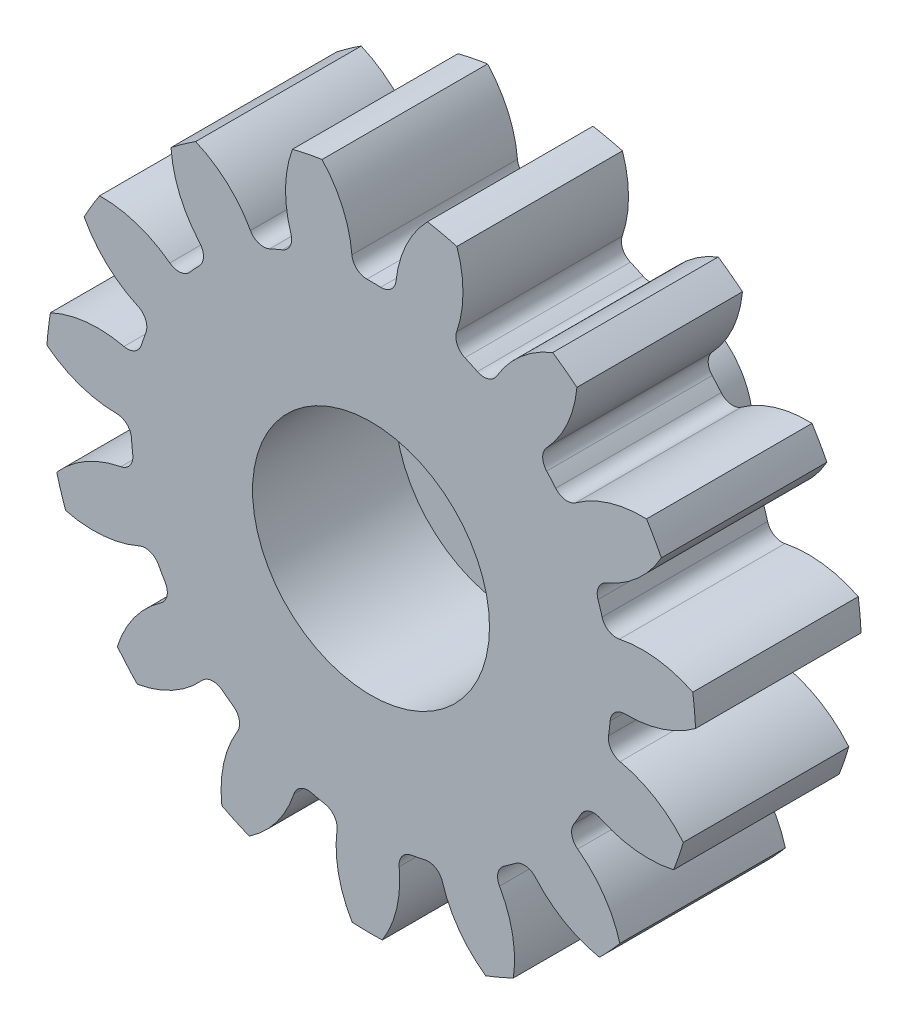
SolidWorks part; units mm, degrees
material "ABS"
ref_plane "Front" through (0, 0, 0) normal (0, 0, 1) x (1, 0, 0)
ref_plane "Top" through (0, 0, 0) normal (0, 1, 0) x (1, 0, 0)
ref_plane "Right" through (0, 0, 0) normal (1, 0, 0) x (0, 0, -1)
sketch "Sketch3" plane through (0, 0, 0) normal (0, 0, 1) x (1, 0, 0)
  circle A0 centre (0, 0) radius 21.59
  dimension "od" = 43.18
extrude "gearBody" add sketch "Sketch3" along normal blind 11
sketch "Sketch2" plane through (0, 0, 0) normal (0, 0, 1) x (1, 0, 0)
  line L0 (0, 0) -> (17.0393, 7.0579) construction
  line L1 (22.0105, -8.0941) -> (0, 0) construction
  line L2 (0, 0) -> (36.3143, 0) construction
  line L3 (19.0486, -0.229) -> (18.5878, -4.1711) construction
  line L5 (18.8182, -2.2) -> (0, 0) construction
  line L7 (0, 0) -> (18.4432, 0) construction
  arc A0 (18.4395, -0.3701) -> (18.0276, -3.8932) centre (0, 0) ccw construction
  arc A1 (21.5666, 1.0048) -> (20.7532, -5.9524) centre (0, 0) ccw construction
  arc A2 (19.0486, -0.229) -> (18.5878, -4.1711) centre (0, 0) ccw construction
  arc A3 (15.7838, -2.3046) -> (15.8898, -1.3984) centre (0, 0) ccw
  arc A4 (22.0105, -8.0941) -> (16.5506, -3.4102) centre (14.9518, -10.798) ccw
  arc A5 (22.0105, -8.0941) -> (23.2839, 2.7987) centre (0, 0) ccw
  arc A6 (23.2839, 2.7987) -> (16.8909, -0.4995) centre (17.0393, 7.0579) cw
  arc A7 (15.8898, -1.3984) -> (16.8909, -0.4995) centre (16.8715, -1.4848) cw
  arc A8 (16.5506, -3.4102) -> (15.7838, -2.3046) centre (16.759, -2.4469) cw
  point P6 (23.2839, 2.7987)
  point P22 (22.0105, -8.0941)
  dimension "baseDia" = 36.8864
  dimension "od" = 43.18
  dimension "pd" = 38.1
  dimension "rd" = 31.9024
  dimension "rFillet" = 0.9855
  dimension "pointX" = 23.2839
  dimension "pointY" = 2.7987
  dimension "CTT" = 3.9421
  dimension "flankCenterAngle" = 22.5
extrude "toothCut" cut sketch "Sketch2" along normal through all
pattern_circular "CirPattern1" count 15 over 360 about axis through (0, 0, 11) along (0, 0, -1) of "toothCut"
sketch "hub1Dia" plane through (0, 0, 0) normal (0, 0, -1) x (-1, 0, 0)
  circle A0 centre (0, 0) radius 12.7
  dimension "hub1Dia" = 25.4
sketch "hub2Dia" plane through (0, 0, 11) normal (0, 0, 1) x (1, 0, 0)
  circle A0 centre (0, 0) radius 12.7
  dimension "hub2dia" = 25.4
sketch "boreDia" plane through (0, 0, 0) normal (0, 0, 1) x (1, 0, 0)
  circle A0 centre (0, 0) radius 7.874
  dimension "boreDia" = 15.748
extrude "bore" cut sketch "boreDia" against normal mid plane 25400
sketch "Sketch4" plane through (0, 0, 0) normal (1, 0, 0) x (0, 0, -1)
  line L0 (0, 0) -> (29.4347, 0) construction
  line L1 (0, 0) -> (9.525, 0)
  line L2 (9.525, 0) -> (9.525, 4.826)
  line L3 (9.525, 4.826) -> (5.588, 4.826)
  line L4 (0, 0) -> (-1.524, 0)
  line L5 (-1.524, 0) -> (-1.524, 7.874)
  line L6 (-1.524, 7.874) -> (0, 7.874)
  line L7 (0, 12.2181) -> (0, 16.6995) construction
  line L8 (0, 7.874) -> (0, 10.414)
  arc A0 (0, 10.414) -> (5.588, 4.826) centre (5.588, 10.414) ccw
  dimension "D3" = 5.588
  dimension "D1" = 15.748
  dimension "D2" = 9.652
  dimension "D4" = 1.524
  dimension "D5" = 9.525
revolve "Revolve1" add sketch "Sketch4" angle 360 about L0
sketch "Sketch6" plane through (0, 0, -9.525) normal (0, 0, -1) x (-1, 0, 0)
  circle A0 centre (0, 0) radius 4.1
  dimension "D1" = 8.2
extrude "Cut-Extrude1" cut sketch "Sketch6" against normal blind 5.3
equation "\"Mid_Tube_Length\"= 1in"
equation "\"Bodytube_OD\"= 6.17in"
equation "\"Bodytube_ID\"= 5.998in"
equation "\"Camera_Cutout_Width\"=10mm"
equation "\"Camera_Cutout_Height\"=7mm"
equation "\"Fwd_Tube_Length\"= 40in"
equation "\"BKHD_Screw_Diam\"= 3.5mm"
equation "\"Fwd_BKHD_From_Top\"= 18in"
equation "\"Shear_Screw_Diameter\"= 0.086in"
equation "\"Shear_Screw_Coupler_Location\"= 4.5in"
equation "\"Motor_OD\"= 4in"
equation "\"Mid_Coupler_Length\"= 13in"
equation "\"Aft_Section_Length\"= 39in"
equation "\"AB_Coupler_OD_Length\"= 1in"
equation "\"AB_Coupling_Section_Length\"= 0.375in"
equation "\"AB_Coupler_Length\"= \"AB_Coupler_OD_Length\" + \"AB_Coupling_Section_Length\" * 2"
equation "\"Cutout_Angle\"= 80"
equation "\"AB_Paddle_Height\"= 0.375in"
equation "\"AB_Coupler_Num_Screws\"= 4"
equation "\"AB_BKHD_Thickness\"= 0.375in"
equation "\"AB_Mount_From_Bottom\"= 23.175in"
equation "\"Num_Cutouts\"= 3"
equation "\"AB_Coupler_OD\"= 6.17in"
equation "\"AB_Coupler_ID\"= 5.75in"
equation "\"AB_Coupler_Surface_Diameter\"= 5.998in"
equation "\"AB_Coupling_Screw_Diameter\"= 0.15748in"
equation "\"AB_Central_Bushing_Length\"= .4724in"
equation "\"Lead_Screw_Dist\"= 3.4in"
equation "\"Lead_Screw_Diam\"= 0.386in"
equation "\"Lead_Screw_Length\"= (\"Mid_Coupler_Length\" + 2*0.375in + 2*0.5in)"
equation "\"Paddle_Pin_Offset\"= .25in"
equation "\"Paddle_Pin_Radius\"= 2.25in"
equation "\"SS_Paddle_Pin_Radius\"= 2.25*0.66in"
equation "\"Paddle_Gear_OD\"= 3.2in"
equation "\"Drive_Gear_OD\"= 1.7in"
equation "\"Fin_Thickness\"= .118in"
equation "\"Guiderail_Cutout_Diameter\"= 1.5in"
equation "\"DB9_Hole_Dist\"= 25mm"
equation "\"DB9_Relief_Width\"= 0.47in"
equation "\"DB9_Relief_Hole_Offset\"= 0.09in"
equation "\"Airbrakes_Wire_Hole_Dia\"= .25in"
equation "\"Airbrakes_Wire_Hole_Dist\"= 1.1in"
equation "\"Servo_Gear_Offset\"= 0.5in"
equation "\"FWD_Shear_Screw_Dist\"= 1.5in"
equation "\"Camera_Screw_Dia\"= 0.216535"
equation "\"Camera_Hole_Angle\"= atn ( 2 / 3 * tan ( 12.5deg ) )"
equation "\"Coupler_OD\"= 5.998"
equation "\"Coupler_ID\"= 5.8"
equation "\"Mounting_Bracket_Centerhole_DIA\" = 0.4in"
equation "\"Drive_Gear_Shaft_DIA\" = \"Mounting_Bracket_Centerhole_DIA\" - 0.02in"
equation "\"Drive_Gear_Fillet\" = 0.22in"
equation "\"Drive_Gear_ID\" = 0.62in"
equation "\"Drive_Gear_Offset\" = 0.01in"
equation "\"D2@Sketch4\"=\"Drive_Gear_Shaft_DIA\""
equation "\"D1@Sketch4\"=\"Drive_Gear_ID\""
equation "\"D3@Sketch4\"=\"Drive_Gear_Fillet\""
